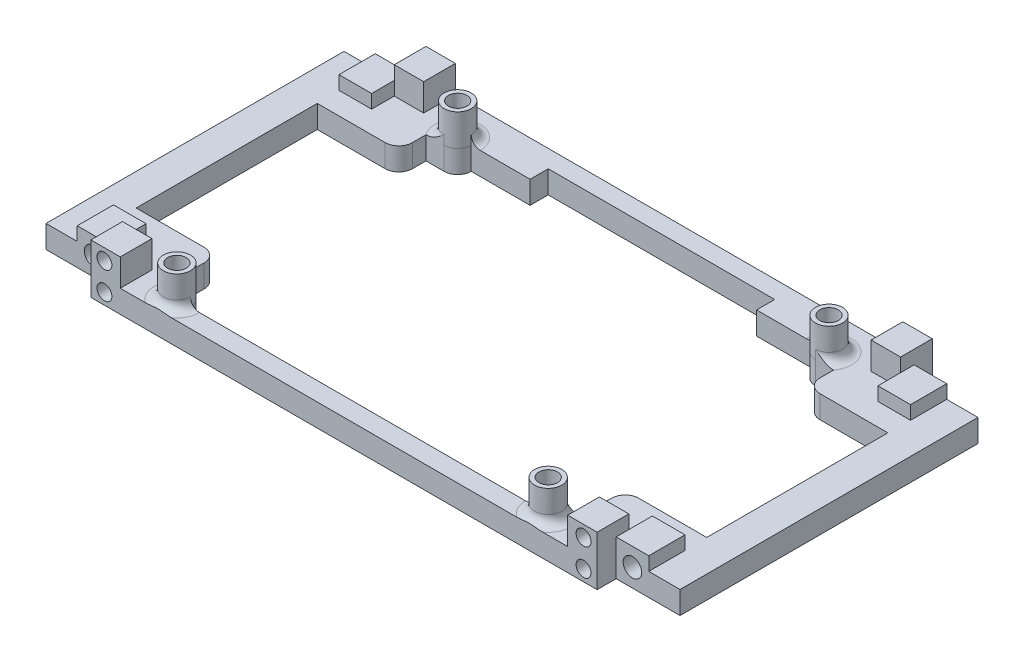
SolidWorks part; units mm, degrees
ref_plane "Front Plane" through (0, 0, 0) normal (0, 0, 1) x (1, 0, 0)
ref_plane "Top Plane" through (0, 0, 0) normal (0, 1, 0) x (1, 0, 0)
ref_plane "Right Plane" through (0, 0, 0) normal (1, 0, 0) x (0, 0, -1)
sketch "Sketch1" plane through (0, 0, 0) normal (0, 1, 0) x (1, 0, 0)
  line L0 (-70, -32.9) -> (-70, 32.9)
  line L1 (-70, -40) -> (70, -40) construction
  line L2 (-70, -40) -> (-70, 40) construction
  line L3 (-70, 40) -> (70, 40) construction
  line L4 (70, -40) -> (70, 40) construction
  line L5 (-70, -40) -> (70, 40) construction
  line L6 (-70, 40) -> (70, -40) construction
  line L7 (-70, 32.9) -> (-55.9, 32.9)
  line L8 (-55.9, 32.9) -> (-55.9, 40)
  line L9 (-55.9, 40) -> (55.9, 40)
  line L10 (55.9, 40) -> (55.9, 32.9)
  line L11 (55.9, 32.9) -> (70, 32.9)
  line L12 (70, 32.9) -> (70, -32.9)
  line L13 (70, -32.9) -> (55.9, -32.9)
  line L14 (55.9, -32.9) -> (55.9, -40)
  line L15 (55.9, -40) -> (-55.9, -40)
  line L16 (-55.9, -40) -> (-55.9, -32.9)
  line L17 (-55.9, -32.9) -> (-70, -32.9)
  point P0 (0, 0)
  dimension "D1" = 140
  dimension "D2" = 80
  dimension "D3" = 7.1
  dimension "D4" = 14.1
extrude "Boss-Extrude1" add sketch "Sketch1" along normal blind 5
sketch "Sketch3" plane through (0, 5, 0) normal (0, 1, 0) x (1, 0, 0)
  line L1 (-41, 29) -> (41, 29) construction
  line L2 (-41, 29) -> (-41, -33) construction
  line L3 (-41, -33) -> (41, -33) construction
  line L4 (41, 29) -> (41, -33) construction
  line L5 (-41, 29) -> (41, -33) construction
  line L6 (-41, -33) -> (41, 29) construction
  circle A0 centre (-41, -33) radius 3
  circle A1 centre (41, -33) radius 3
  circle A2 centre (41, 29) radius 3
  circle A3 centre (-41, 29) radius 3
  point P0 (0, -2)
  dimension "D4" = 6
  dimension "D1" = 82
  dimension "D2" = 62
  dimension "D3" = 2
sketch "Sketch2" plane through (0, 5, 0) normal (0, 1, 0) x (1, 0, 0)
  line L0 (-41, 26) -> (-38, 26)
  line L5 (-38, -33) -> (38, -33)
  line L6 (-41, -30) -> (-41, 26)
  line L7 (-38, 29) -> (38, 29)
  line L8 (41, -30) -> (41, 26)
  line L9 (-41, -33) -> (41, 29) construction
  line L10 (-41, 29) -> (41, -33) construction
  line L11 (-38, 26) -> (-38, 29)
  line L12 (38, 29) -> (38, 26)
  line L13 (38, 26) -> (41, 26)
  line L14 (41, -30) -> (38, -30)
  line L15 (38, -30) -> (38, -33)
  line L16 (-38, -33) -> (-38, -30)
  line L17 (-38, -30) -> (-41, -30)
  line L18 (41, -33) -> (-41, -33) construction
  line L19 (-41, -33) -> (-41, 29) construction
  line L20 (-41, 29) -> (41, 29) construction
  line L21 (41, 29) -> (41, -33) construction
  point P0 (0, 0)
  point P1 (0, -2)
  dimension "D1" = 3
extrude "Cut-Extrude1" cut sketch "Sketch2" against normal through all
extrude "Boss-Extrude2" add sketch "Sketch3" along normal blind 7
sketch "Sketch4" plane through (0, 12, 0) normal (0, 1, 0) x (1, 0, 0)
  circle A0 centre (-41, 29) radius 2.05
  circle A1 centre (41, 29) radius 2.05
  circle A2 centre (41, -33) radius 2.05
  circle A3 centre (-41, -33) radius 2.05
  dimension "D1" = 4.1
extrude "Cut-Extrude2" cut sketch "Sketch4" against normal through all and the other way through all
sketch "Sketch5" plane through (0, 5, 0) normal (0, 1, 0) x (1, 0, 0)
  line L0 (-41, -30) -> (-38, -30) construction
  line L1 (-41, 26) -> (-53, 26)
  line L2 (-41, 26) -> (-41, -30)
  line L3 (-41, -30) -> (-53, -30)
  line L4 (-53, 26) -> (-53, -30)
  line L5 (0, 29) -> (0, -33) construction
  line L6 (38, 29) -> (-38, 29) construction
  line L7 (-38, -33) -> (38, -33) construction
  line L8 (53, 26) -> (53, -30)
  line L9 (41, -30) -> (53, -30)
  line L10 (41, 26) -> (41, -30)
  line L11 (41, 26) -> (53, 26)
  dimension "D1" = 12
extrude "Cut-Extrude3" cut sketch "Sketch5" against normal through all
fillet "Fillet1" radius 3 4 edges at (38, 2.5, 30) (-38, 2.5, 30) (38, 2.5, -26) (-38, 2.5, -26)
sketch "Sketch6" plane through (0, 5, 0) normal (0, 1, 0) x (1, 0, 0)
  line L0 (38, 29) -> (-38, 29) construction
  line L1 (-25, 29) -> (25, 29)
  line L2 (-25, 29) -> (-25, 33)
  line L3 (-25, 33) -> (25, 33)
  line L4 (25, 29) -> (25, 33)
  line L5 (0, -33) -> (0, -40) construction
  line L6 (-38, -33) -> (38, -33) construction
  line L7 (-55.9, -40) -> (55.9, -40) construction
  line L8 (0, 33) -> (0, 40) construction
  line L9 (55.9, 40) -> (-55.9, 40) construction
  point P6 (0, 33)
  dimension "D1" = 50
extrude "Cut-Extrude4" cut sketch "Sketch6" against normal through all
sketch "Sketch7" plane through (0, 5, 0) normal (0, 1, 0) x (1, 0, 0)
  line L0 (0, 40) -> (0, -40) construction
  line L1 (55.9, 32.9) -> (63.1, 32.9)
  line L2 (55.9, 32.9) -> (55.9, 24.9)
  line L3 (55.9, 24.9) -> (63.1, 24.9)
  line L4 (63.1, 32.9) -> (63.1, 24.9)
  line L5 (55.9, 40) -> (-55.9, 40) construction
  line L6 (-55.9, -40) -> (55.9, -40) construction
  line L7 (-70, 0) -> (70, 0) construction
  line L8 (-70, 32.9) -> (-70, -32.9) construction
  line L9 (70, -32.9) -> (70, 32.9) construction
  dimension "D1" = 7.2
  dimension "D2" = 8
extrude "Boss-Extrude3" add sketch "Sketch7" along normal blind 3
sketch "Sketch8" plane through (0, 0, -32.9) normal (0, 0, -1) x (-1, 0, 0)
  line L0 (-63.1, 8) -> (-55.9, 0) construction
  circle A0 centre (-59.5, 4) radius 2.05
  dimension "D1" = 4.1
extrude "Cut-Extrude5" cut sketch "Sketch8" against normal blind 6
mirror "Mirror3" about plane through (0, 0, 0) normal (1, 0, 0) of "Cut-Extrude5", "Boss-Extrude3"
mirror "Mirror4" about plane through (0, 0, 0) normal (0, 0, 1) of "Mirror3"
sketch "Sketch10" plane through (0, 5, 0) normal (0, 1, 0) x (1, 0, 0)
  line L0 (55.9, 32.9) -> (55.9, 40) construction
  line L1 (-55.9, 40) -> (55.9, 40)
  line L2 (-55.9, 40) -> (-55.9, 39)
  line L3 (-55.9, 39) -> (55.9, 39)
  line L4 (55.9, 40) -> (55.9, 39)
  line L5 (-55.9, -32.9) -> (-55.9, -40) construction
  line L6 (55.9, -40) -> (-55.9, -40)
  line L7 (55.9, -40) -> (55.9, -39)
  line L8 (55.9, -39) -> (-55.9, -39)
  line L9 (-55.9, -40) -> (-55.9, -39)
  dimension "D1" = 1
  dimension "D2" = 1
extrude "Cut-Extrude7" cut sketch "Sketch10" against normal through all
fillet "Fillet5" radius 2 4 edges at (43.1213, 5, -31.1213) (43.1213, 5, 35.1213) (-43.1213, 5, 35.1213) (-43.1213, 5, -31.1213)
sketch "Sketch11" plane through (0, 5, 0) normal (0, 1, 0) x (1, 0, 0)
  line L1 (53, -30) -> (45, -30)
  line L2 (53, -30) -> (53, 26)
  line L3 (53, 26) -> (45, 26)
  line L4 (45, -30) -> (45, 26)
  line L5 (-45, -30) -> (-53, -30)
  line L6 (-45, -30) -> (-45, 26)
  line L7 (-45, 26) -> (-53, 26)
  line L8 (-53, -30) -> (-53, 26)
extrude "Boss-Extrude4" add sketch "Sketch11" against normal up to surface (5 mm away) up to face at (0, 0, 0)
sketch "Sketch12" plane through (0, 5, 0) normal (0, 1, 0) x (1, 0, 0)
  line L0 (45, 26) -> (45, -30) construction
  line L1 (45, 20) -> (63, 20)
  line L2 (45, 20) -> (45, -20)
  line L3 (45, -20) -> (63, -20)
  line L4 (63, 20) -> (63, -20)
  line L5 (70, -32.9) -> (70, 32.9) construction
  point P6 (63, 0)
  point P9 (70, 0)
  dimension "D1" = 18
  dimension "D2" = 40
extrude "Cut-Extrude8" cut sketch "Sketch12" against normal through all and the other way through all
mirror "Mirror7" about plane through (0, 0, 0) normal (1, 0, 0) of "Cut-Extrude8"
fillet "Fillet6" radius 3 4 edges at (45, 2.5, -20) (45, 2.5, 20) (-45, 2.5, -20) (-45, 2.5, 20)
sketch "Sketch13" plane through (0, 5, 0) normal (0, 1, 0) x (1, 0, 0)
  line L0 (55.9, 32.9) -> (55.9, 39) construction
  line L1 (-55.9, 39) -> (55.9, 39)
  line L2 (-55.9, 39) -> (-55.9, 36.9)
  line L3 (-55.9, 36.9) -> (55.9, 36.9)
  line L4 (55.9, 39) -> (55.9, 36.9)
  line L5 (-55.9, -32.9) -> (-55.9, -39) construction
  line L6 (55.9, -39) -> (-55.9, -39)
  line L7 (55.9, -39) -> (55.9, -37.1)
  line L8 (55.9, -37.1) -> (-55.9, -37.1)
  line L9 (-55.9, -39) -> (-55.9, -37.1)
  dimension "D1" = 2.1
  dimension "D2" = 1.9
extrude "Cut-Extrude9" cut sketch "Sketch13" against normal through all both and the other way through all
sketch "Sketch14" plane through (0, 5, 0) normal (0, 1, 0) x (1, 0, 0)
  line L1 (-55.9, -37.1) -> (-49.4, -37.1)
  line L2 (-55.9, -37.1) -> (-55.9, -30.1)
  line L3 (-55.9, -30.1) -> (-49.4, -30.1)
  line L4 (-49.4, -37.1) -> (-49.4, -30.1)
  line L5 (-55.9, 36.9) -> (-49.4, 36.9)
  line L6 (-55.9, 36.9) -> (-55.9, 29.9)
  line L7 (-55.9, 29.9) -> (-49.4, 29.9)
  line L8 (-49.4, 36.9) -> (-49.4, 29.9)
  dimension "D1" = 6.5
  dimension "D2" = 7
extrude "Boss-Extrude5" add sketch "Sketch14" along normal blind 6
sketch "Sketch15" plane through (0, 0, 37.1) normal (0, 0, 1) x (1, 0, 0)
  line L0 (-49.4, 5) -> (-49.4, 0) construction
  line L1 (55.9, 0) -> (-55.9, 0) construction
  line L3 (-55.9, 0) -> (-55.9, 11) construction
  circle A0 centre (-52.9, 2.5) radius 1.65
  circle A1 centre (-52.9, 8.5) radius 1.65
  point P4 (-49.4, 2.5)
  dimension "D1" = 3.3
  dimension "D2" = 3
  dimension "D3" = 6
extrude "Cut-Extrude10" cut sketch "Sketch15" against normal blind 6
sketch "Sketch16" plane through (0, 0, -36.9) normal (0, 0, -1) x (-1, 0, 0)
  circle A0 centre (52.9, 8.5) radius 1.65 construction
  circle A1 centre (52.9, 2.5) radius 1.65 construction
  circle A2 centre (52.9, 8.5) radius 1.65
  circle A3 centre (52.9, 2.5) radius 1.65
extrude "Cut-Extrude11" cut sketch "Sketch16" against normal blind 6
mirror "Mirror8" about plane through (0, 0, 0) normal (1, 0, 0) of "Cut-Extrude10", "Cut-Extrude11", "Boss-Extrude5"
